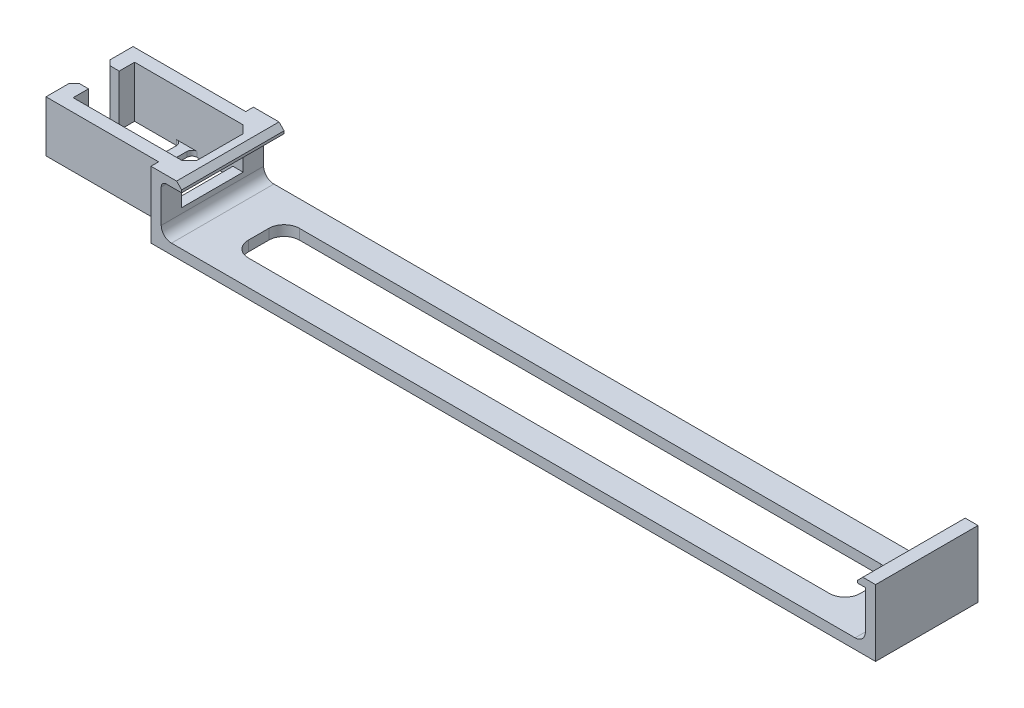
SolidWorks part; units mm, degrees
ref_plane "Front Plane" through (0, 0, 0) normal (0, 0, 1) x (1, 0, 0)
ref_plane "Top Plane" through (0, 0, 0) normal (0, 1, 0) x (1, 0, 0)
ref_plane "Right Plane" through (0, 0, 0) normal (1, 0, 0) x (0, 0, -1)
sketch "Sketch1" plane through (0, 0, 0) normal (0, 1, 0) x (1, 0, 0)
  line L1 (-70.75, 10) -> (70.75, 10)
  line L2 (-70.75, 10) -> (-70.75, -10)
  line L3 (-70.75, -10) -> (70.75, -10)
  line L4 (70.75, 10) -> (70.75, -10)
  line L5 (-70.75, 10) -> (70.75, -10) construction
  line L6 (-70.75, -10) -> (70.75, 10) construction
  point P0 (0, 0)
  dimension "D1" = 141.5
  dimension "D2" = 20
extrude "Boss-Extrude1" add sketch "Sketch1" along normal blind 2
sketch "Sketch2" plane through (0, 2, 0) normal (0, 1, 0) x (1, 0, 0)
  line L0 (-70.75, -10) -> (70.75, -10) construction
  line L1 (70.75, 10) -> (68.75, 10)
  line L2 (70.75, 10) -> (70.75, -10)
  line L3 (70.75, -10) -> (68.75, -10)
  line L4 (68.75, 10) -> (68.75, -10)
  line L6 (-70.75, 10) -> (-68.75, 10)
  line L7 (-70.75, 10) -> (-70.75, -10)
  line L8 (-70.75, -10) -> (-68.75, -10)
  line L9 (-68.75, 10) -> (-68.75, -10)
  dimension "D1" = 2
  dimension "D2" = 2
extrude "Boss-Extrude2" add sketch "Sketch2" along normal blind 11
sketch "Sketch3" plane through (68.75, 0, 0) normal (-1, 0, 0) x (0, 0, 1)
  line L0 (-10, 13) -> (-10, 2) construction
  line L1 (10, 13) -> (-10, 13)
  line L2 (10, 13) -> (10, 11.5)
  line L3 (10, 11.5) -> (-10, 11.5)
  line L4 (-10, 13) -> (-10, 11.5)
  dimension "D1" = 1.5
extrude "Boss-Extrude3" add sketch "Sketch3" along normal blind 1.5
chamfer "Chamfer1" distance 1 angle 45 1 edges at (67.25, 13, 0)
sketch "Sketch4" plane through (-68.75, 0, 0) normal (1, 0, 0) x (0, 0, -1)
  line L0 (10, 13) -> (10, 2) construction
  line L1 (-10, 13) -> (10, 13)
  line L2 (-10, 13) -> (-10, 11.5)
  line L3 (-10, 11.5) -> (10, 11.5)
  line L4 (10, 13) -> (10, 11.5)
  dimension "D1" = 1.5
extrude "Boss-Extrude4" add sketch "Sketch4" along normal blind 4
chamfer "Chamfer2" distance 1 angle 45 1 edges at (-64.75, 13, 0)
sketch "Sketch5" plane through (-68.75, 0, 0) normal (1, 0, 0) x (0, 0, -1)
  line L0 (-10, 11.5) -> (-10, 2) construction
  line L1 (-6, 5) -> (6, 5)
  line L2 (-6, 5) -> (-6, 19.3249)
  line L3 (-6, 19.3249) -> (6, 19.3249)
  line L4 (6, 5) -> (6, 19.3249)
  line L5 (-10, 2) -> (10, 2) construction
  dimension "D1" = 12
  dimension "D2" = 4
  dimension "D3" = 3
extrude "Cut-Extrude1" cut sketch "Sketch5" against normal blind 11.5 and the other way blind 1.5
sketch "Sketch6" plane through (-70.75, 0, 0) normal (-1, 0, 0) x (0, 0, 1)
  line L0 (-10, 13) -> (-6, 13) construction
  line L1 (-8.5, 13) -> (-6, 13)
  line L2 (-8.5, 13) -> (-8.5, 3)
  line L3 (-8.5, 3) -> (-6, 3)
  line L4 (-6, 13) -> (-6, 3)
  line L5 (6, 13) -> (10, 13) construction
  line L6 (8.5, 13) -> (6, 13)
  line L7 (8.5, 13) -> (8.5, 3)
  line L8 (8.5, 3) -> (6, 3)
  line L9 (6, 13) -> (6, 3)
  line L10 (-6, 5) -> (6, 5) construction
  line L11 (-6, 13) -> (-6, 5) construction
  dimension "D1" = 2.5
  dimension "D2" = 2.5
  dimension "D3" = 2
  dimension "D4" = 2
  dimension "D5" = 0
extrude "Boss-Extrude5" add sketch "Sketch6" along normal blind 22
sketch "Sketch7" plane through (0, 0, 6) normal (0, 0, -1) x (-1, 0, 0)
  line L0 (92.75, 3) -> (70.75, 3) construction
  line L1 (92.75, 13) -> (89.95, 13)
  line L2 (92.75, 13) -> (92.75, 3)
  line L3 (92.75, 3) -> (89.95, 3)
  line L4 (89.95, 13) -> (89.95, 3)
  dimension "D1" = 2.8
extrude "Boss-Extrude6" add sketch "Sketch7" along normal blind 3
sketch "Sketch8" plane through (0, 0, -6) normal (0, 0, 1) x (1, 0, 0)
  line L0 (-92.75, 3) -> (-70.75, 3) construction
  line L1 (-92.75, 13) -> (-89.95, 13)
  line L2 (-92.75, 13) -> (-92.75, 3)
  line L3 (-92.75, 3) -> (-89.95, 3)
  line L4 (-89.95, 13) -> (-89.95, 3)
  dimension "D1" = 2.8
extrude "Boss-Extrude7" add sketch "Sketch8" along normal blind 3
chamfer "Chamfer3" distance 1 angle 45 2 edges at (-92.75, 8, -3) (-92.75, 8, 3)
sketch "Sketch9" plane through (0, 3, 0) normal (0, -1, 0) x (1, 0, 0)
  line L0 (-92.75, 8.5) -> (-70.75, 8.5) construction
  line L1 (-80.75, 8.5) -> (-78.75, 8.5)
  line L2 (-80.75, 8.5) -> (-80.75, -8.5)
  line L3 (-80.75, -8.5) -> (-78.75, -8.5)
  line L4 (-78.75, 8.5) -> (-78.75, -8.5)
  line L5 (-92.75, -8.5) -> (-70.75, -8.5) construction
  line L6 (-70.75, -10) -> (-70.75, 10) construction
  dimension "D1" = 2
  dimension "D2" = 8
extrude "Boss-Extrude8" add sketch "Sketch9" against normal blind 1
fillet "Fillet1" radius 1 4 edges at (-80.75, 3.5, -6) (-78.75, 3.5, -6) (-80.75, 3.5, 6) (-78.75, 3.5, 6)
fillet "Fillet2" radius 2 2 edges at (-68.75, 2, 0) (68.75, 2, 0)
sketch "Sketch11" plane through (0, 2, 0) normal (0, 1, 0) x (1, 0, 0)
  line L0 (66.75, 10) -> (-66.75, 10) construction
  line L1 (-59.75, 5) -> (59.75, 5)
  line L2 (-59.75, 5) -> (-59.75, -5)
  line L3 (-59.75, -5) -> (59.75, -5)
  line L4 (59.75, 5) -> (59.75, -5)
  line L5 (-66.75, -10) -> (66.75, -10) construction
  line L6 (-66.75, 10) -> (-66.75, -10) construction
  line L7 (66.75, -10) -> (66.75, 10) construction
  dimension "D1" = 5
  dimension "D2" = 5
  dimension "D3" = 7
  dimension "D4" = 7
extrude "Cut-Extrude2" cut sketch "Sketch11" against normal blind 10
fillet "Fillet3" radius 3 4 edges at (59.75, 1, 5) (59.75, 1, -5) (-59.75, 1, 5) (-59.75, 1, -5)
chamfer "Chamfer4" distance 1.5 angle 45 2 edges at (-67.25, 12.25, 6) (-67.25, 12.25, -6)
fillet "Fillet4" radius 1 2 edges at (-68.75, 11.5, 8) (-68.75, 11.5, -8)
